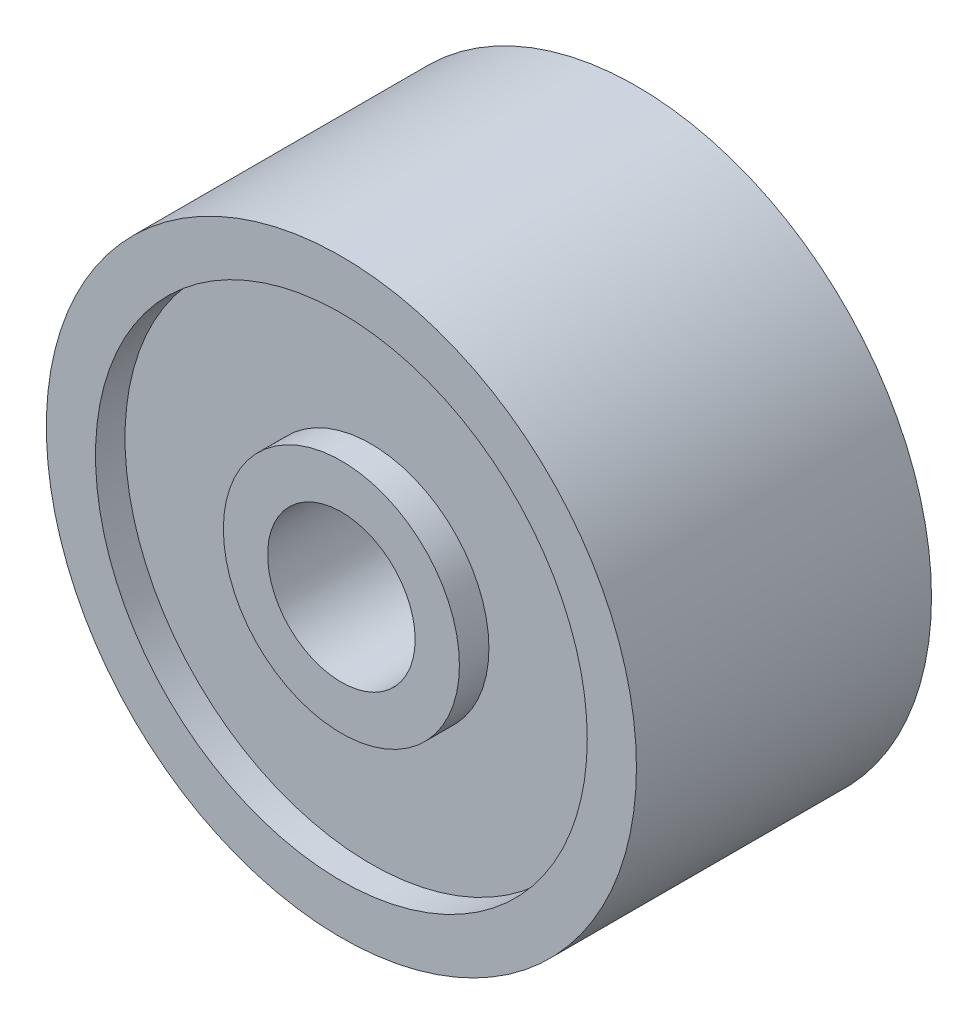
SolidWorks part; units mm, degrees
ref_plane "Front Plane" through (0, 0, 0) normal (0, 0, 1) x (1, 0, 0)
ref_plane "Top Plane" through (0, 0, 0) normal (0, 1, 0) x (1, 0, 0)
ref_plane "Right Plane" through (0, 0, 0) normal (1, 0, 0) x (0, 0, -1)
sketch "Sketch1" plane through (0, 0, 0) normal (0, 0, 1) x (1, 0, 0)
  circle A0 centre (0, 0) radius 0.75
  circle A1 centre (0, 0) radius 3
extrude "Boss-Extrude1" add sketch "Sketch1" along normal blind 3
sketch "Sketch2" plane through (0, 0, 3) normal (0, 0, 1) x (1, 0, 0)
  circle A0 centre (0, 0) radius 1.2
  circle A1 centre (0, 0) radius 2.5
extrude "Cut-Extrude1" cut sketch "Sketch2" against normal blind 0.3
extrude "Cut-Extrude2" cut sketch "Sketch2<2>" along normal blind 0.3 from surface starting at face at (3, 0, 0)
sketch "Sketch2<2>" plane through (0, 0, 3) normal (0, 0, 1) x (1, 0, 0) same geometry as "Sketch2"
